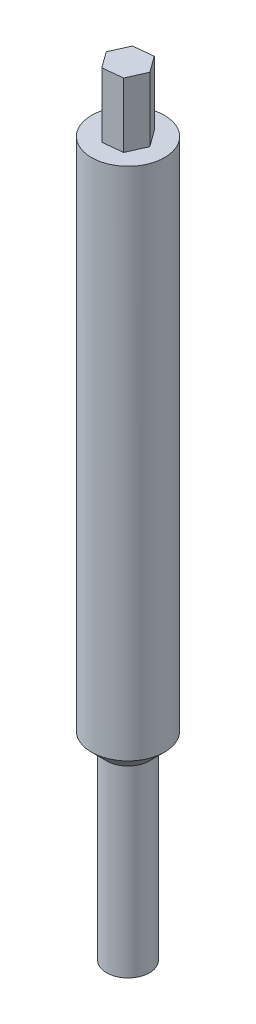
SolidWorks part; units mm, degrees
ref_plane "Front Plane" through (0, 0, 0) normal (0, 0, 1) x (1, 0, 0)
ref_plane "Top Plane" through (0, 0, 0) normal (0, 1, 0) x (1, 0, 0)
ref_plane "Right Plane" through (0, 0, 0) normal (1, 0, 0) x (0, 0, -1)
sketch "Sketch1" plane through (0, 0, 0) normal (0, 1, 0) x (1, 0, 0)
  circle A0 centre (0, 0) radius 6.35
  dimension "D1" = 12.7
extrude "Boss-Extrude1" add sketch "Sketch1" along normal blind 421.64
sketch "Sketch2" plane through (0, 0, 0) normal (0, -1, 0) x (-1, 0, 0)
  circle A0 centre (0, 0) radius 10.795
  dimension "D1" = 21.59
extrude "Boss-Extrude2" add sketch "Sketch2" against normal blind 421.64
sketch "Sketch3" plane through (0, 0, 0) normal (0, -1, 0) x (1, 0, 0)
  circle A0 centre (0, 0) radius 6.35
  circle A1 centre (0, 0) radius 25.4
  dimension "D1" = 12.7
  dimension "D2" = 50.8
extrude "Cut-Extrude1" cut sketch "Sketch3" against normal blind 52.324
sketch "Sketch4" plane through (0, 421.64, 0) normal (0, 1, 0) x (1, 0, 0)
  circle A0 centre (0, 0) radius 6.35
  circle A1 centre (0, 0) radius 25.4
  dimension "D1" = 50.8
  dimension "D2" = 12.7
extrude "Cut-Extrude2" cut sketch "Sketch4" against normal blind 57.658
ref_plane "Plane1" through (0, 210.82, 0) normal (0, 1, 0) x (1, 0, 0)
sketch "Sketch5" plane through (0, 210.82, 0) normal (0, 1, 0) x (1, 0, 0)
  circle A0 centre (0, 0) radius 15.875
  dimension "D1" = 31.75
chamfer "Chamfer1" distance 6.35 angle 45 2 edges at (0, 52.324, -10.795) (0, 363.982, 10.795)
extrude "Cut-Extrude4" cut sketch "Sketch5" along normal through all contours A0
sketch "Sketch6" plane through (0, 210.82, 0) normal (0, 1, 0) x (1, 0, 0)
  line L1 (-3.4368, 4.7537) -> (-5.8352, -0.5995)
  line L2 (-5.8352, -0.5995) -> (-2.3984, -5.3531)
  line L3 (-2.3984, -5.3531) -> (3.4368, -4.7537)
  line L4 (3.4368, -4.7537) -> (5.8352, 0.5995)
  line L5 (5.8352, 0.5995) -> (2.3984, 5.3531)
  line L6 (2.3984, 5.3531) -> (-3.4368, 4.7537)
  circle A0 centre (0, 0) radius 5.08 construction
  dimension "D1" = 10.16
extrude "Boss-Extrude3" add sketch "Sketch6" along normal blind 19.05
